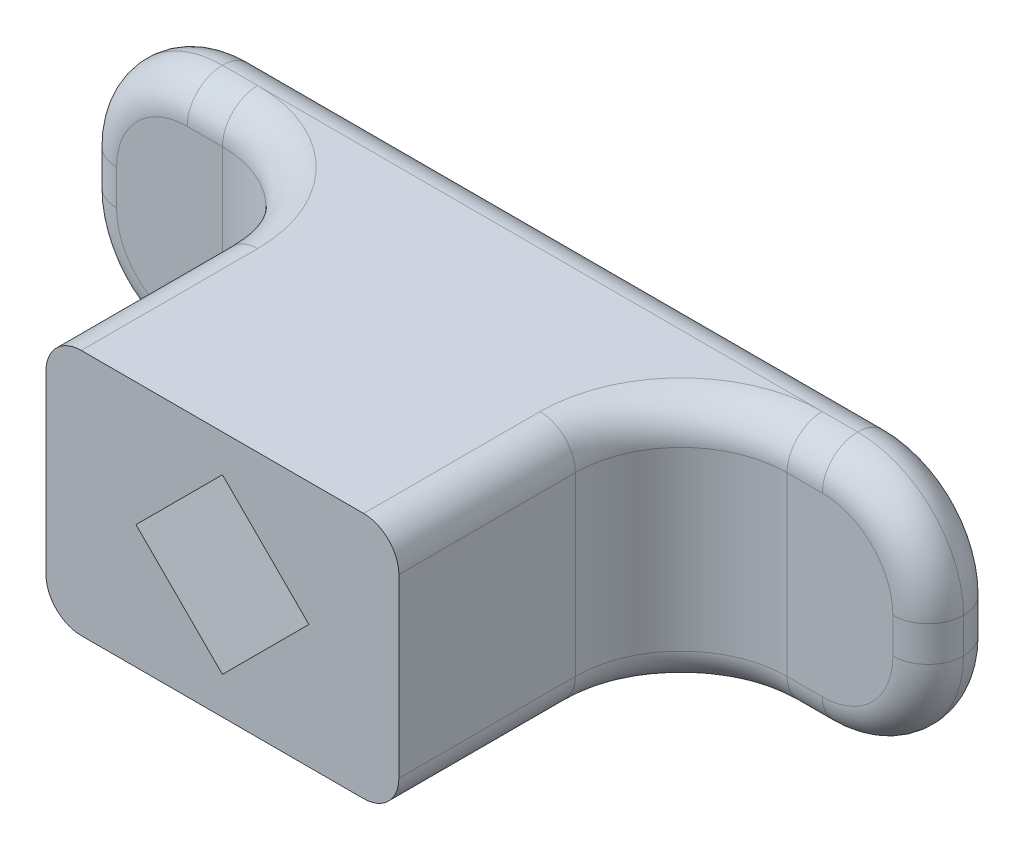
SolidWorks part; units mm, degrees
ref_plane "Front Plane" through (0, 0, 0) normal (0, 0, 1) x (1, 0, 0)
ref_plane "Top Plane" through (0, 0, 0) normal (0, 1, 0) x (1, 0, 0)
ref_plane "Right Plane" through (0, 0, 0) normal (1, 0, 0) x (0, 0, -1)
sketch "Sketch1" plane through (0, 0, 0) normal (0, 1, 0) x (1, 0, 0)
  line L0 (0, 0) -> (0, 10) construction
  line L1 (5, 0) -> (-5, 0)
  line L2 (-5, 8) -> (-12, 8)
  line L3 (5, 8) -> (12, 8)
  line L4 (-12, 8) -> (-12, 10)
  line L5 (12, 8) -> (12, 10)
  line L6 (-12, 10) -> (12, 10)
  line L7 (-5, 8) -> (-5, 0)
  line L8 (5, 8) -> (5, 0)
  dimension "D1" = 2
  dimension "D2" = 10
  dimension "D3" = 10
  dimension "D4" = 24
extrude "Boss-Extrude1" add sketch "Sketch1" along normal mid plane 7
fillet "Fillet1" radius 3 4 edges at (-12, -3.5, -9) (12, -3.5, -9) (12, 3.5, -9) (-12, 3.5, -9)
fillet "Fillet2" radius 3 2 edges at (5, 0, -8) (-5, 0, -8)
fillet "Fillet3" radius 1 26 edges at (5, 3.5, -2.5) (5, -3.5, -2.5) (5.8787, -3.5, -7.1213) (11.1213, -2.6213, -8) (11.1213, 2.6213, -8) (-5, -3.5, -2.5) (-5.8787, -3.5, -7.1213) (-11.1213, -2.6213, -8) (-11.1213, 2.6213, -8) (-5, 3.5, -2.5) (5.8787, 3.5, -7.1213) (-5.8787, 3.5, -7.1213) (0, 3.5, -10) (-11.1213, 2.6213, -10) (-11.1213, -2.6213, -10) (0, -3.5, -10) (11.1213, -2.6213, -10) (11.1213, 2.6213, -10) (12, 0, -8) (-12, 0, -8) (12, 0, -10) (-12, 0, -10) (8.5, -3.5, -8) (8.5, 3.5, -8) (-8.5, -3.5, -8) (-8.5, 3.5, -8)
sketch "Sketch3" plane through (0, 0, 0) normal (0, 0, 1) x (1, 0, 0)
  line L0 (2.45, 0) -> (0, 2.45)
  line L1 (2.45, 0) -> (0, -2.45)
  line L2 (0, 2.45) -> (-2.45, 0)
  line L3 (0, -2.45) -> (-2.45, 0)
  line L4 (2.45, 0) -> (-2.45, 0) construction
  line L5 (0, 2.45) -> (0, -2.45) construction
  circle A1 centre (0, 0) radius 2.45 construction
  point P1 (0, 0)
  dimension "D1" = 4.9
extrude "Cut-Extrude1" cut sketch "Sketch3" against normal blind 4.5
